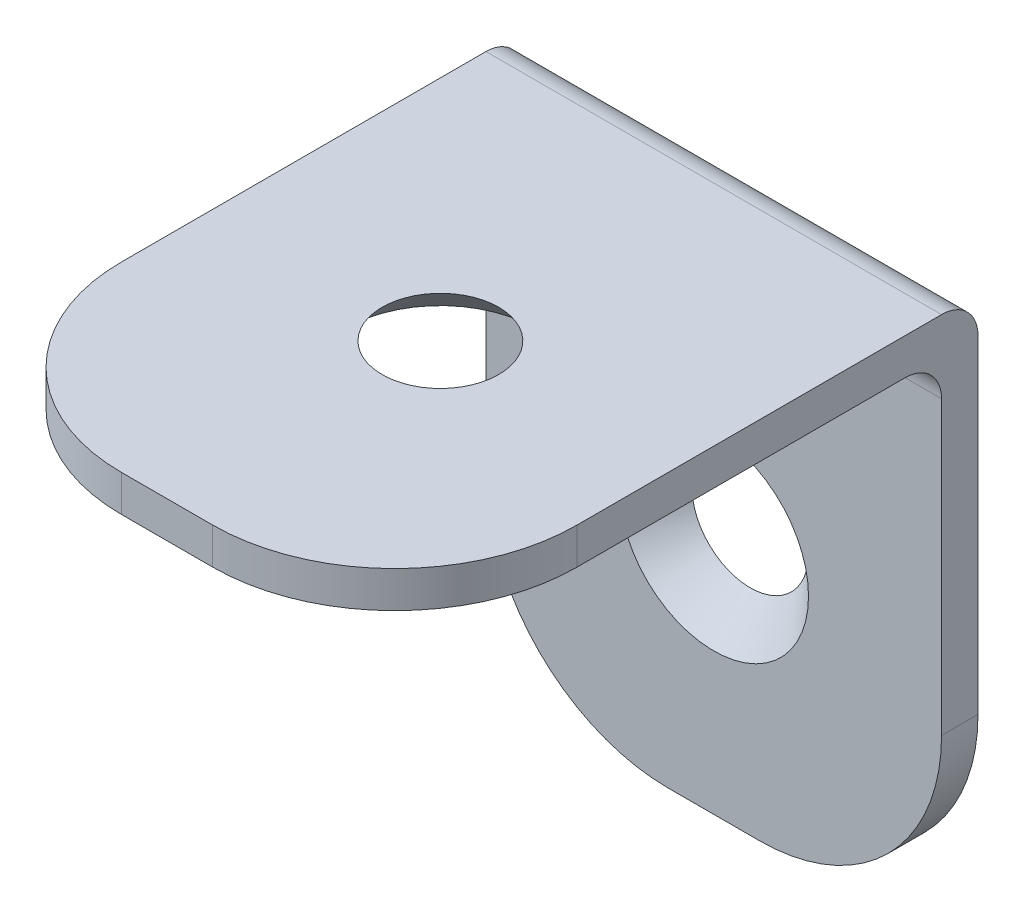
SolidWorks part; units mm, degrees
ref_plane "Спереди" through (0, 0, 0) normal (0, 0, 1) x (1, 0, 0)
ref_plane "Сверху" through (0, 0, 0) normal (0, 1, 0) x (1, 0, 0)
ref_plane "Справа" through (0, 0, 0) normal (1, 0, 0) x (0, 0, -1)
sketch "Эскиз1" plane through (0, 0, 0) normal (0, 1, 0) x (1, 0, 0)
  line L1 (-2.5, -15) -> (2.5, -15)
  line L2 (-12.5, -5) -> (-12.5, 15)
  line L3 (-12.5, 15) -> (12.5, 15)
  line L4 (12.5, -5) -> (12.5, 15)
  line L5 (-12.5, -15) -> (12.5, 15) construction
  line L6 (-12.5, 15) -> (12.5, -15) construction
  arc A0 (2.5, -15) -> (12.5, -5) centre (2.5, -5) ccw
  arc A1 (-2.5, -15) -> (-12.5, -5) centre (-2.5, -5) cw
  point P0 (0, 0)
  dimension "D3" = 10
  dimension "D1" = 25
  dimension "D2" = 30
  dimension "D4" = 15
extrude "Бобышка-Вытянуть1" add sketch "Эскиз1" along normal blind 2
sketch "Эскиз3" plane through (0, 0, -15) normal (0, 0, -1) x (-1, 0, 0)
  line L0 (-2.5, -28) -> (2.5, -28)
  line L1 (-12.5, -18) -> (-12.5, 2)
  line L2 (-12.5, 2) -> (12.5, 2)
  line L3 (12.5, -18) -> (12.5, 2)
  line L4 (-12.5, 0) -> (12.5, 0) construction
  arc A0 (2.5, -28) -> (12.5, -18) centre (2.5, -18) ccw
  arc A1 (-2.5, -28) -> (-12.5, -18) centre (-2.5, -18) cw
  dimension "D1" = 28
  dimension "D2" = 25
extrude "Бобышка-Вытянуть2" add sketch "Эскиз3" along normal blind 2
fillet "Скругление1" radius 2 1 edges at (0, 0, -15)
fillet "Скругление2" radius 2 1 edges at (0, 2, -17)
hole_wizard "Зенковка для винта с полупотайной головкой M52" positions "Эскиз6" profile "Эскиз7" countersink size "M5" standard "ISO" end condition through all
sketch "Эскиз6" plane through (0, 0, -15) normal (0, 0, 1) x (1, 0, 0)
  point P0 (0, -15.0342)
sketch "Эскиз7" plane through (0, -15.0342, -15) normal (1, 0, 0) x (0, -1, 0)
  line L0 (0, 0) -> (0, 2)
  line L1 (0, 2) -> (2.75, 2)
  line L2 (2.75, 2) -> (2.75, 2.45)
  line L3 (2.75, 2.45) -> (5.2, 0)
  line L5 (5.2, 0) -> (0, 0)
  line L6 (-2.75, 2.45) -> (-5.2, 0) construction
  line L11 (0, -6.35) -> (0, 107.95) construction
  dimension "Диаметр сквозного отверстия" = 5.5
  dimension "Глубина сквозного отверстия" = 2
  dimension "Диаметр передней зенковки" = 10.4
  dimension "Угол передней зенковки" = 90
hole_wizard "Зенковка для винта с полупотайной головкой M53" positions "Эскиз8" profile "Эскиз9" countersink size "M5" standard "ISO" end condition through all
sketch "Эскиз8" plane through (0, 0, 0) normal (0, -1, 0) x (-1, 0, 0)
  point P0 (0, 0)
sketch "Эскиз9" plane through (0, 0, 0) normal (1, 0, 0) x (0, 0, -1)
  line L0 (0, 0) -> (0, 2)
  line L1 (0, 2) -> (2.75, 2)
  line L2 (2.75, 2) -> (2.75, 2.45)
  line L3 (2.75, 2.45) -> (5.2, 0)
  line L5 (5.2, 0) -> (0, 0)
  line L6 (-2.75, 2.45) -> (-5.2, 0) construction
  line L11 (0, -6.35) -> (0, 107.95) construction
  dimension "Диаметр сквозного отверстия" = 5.5
  dimension "Глубина сквозного отверстия" = 2
  dimension "Диаметр передней зенковки" = 10.4
  dimension "Угол передней зенковки" = 90
